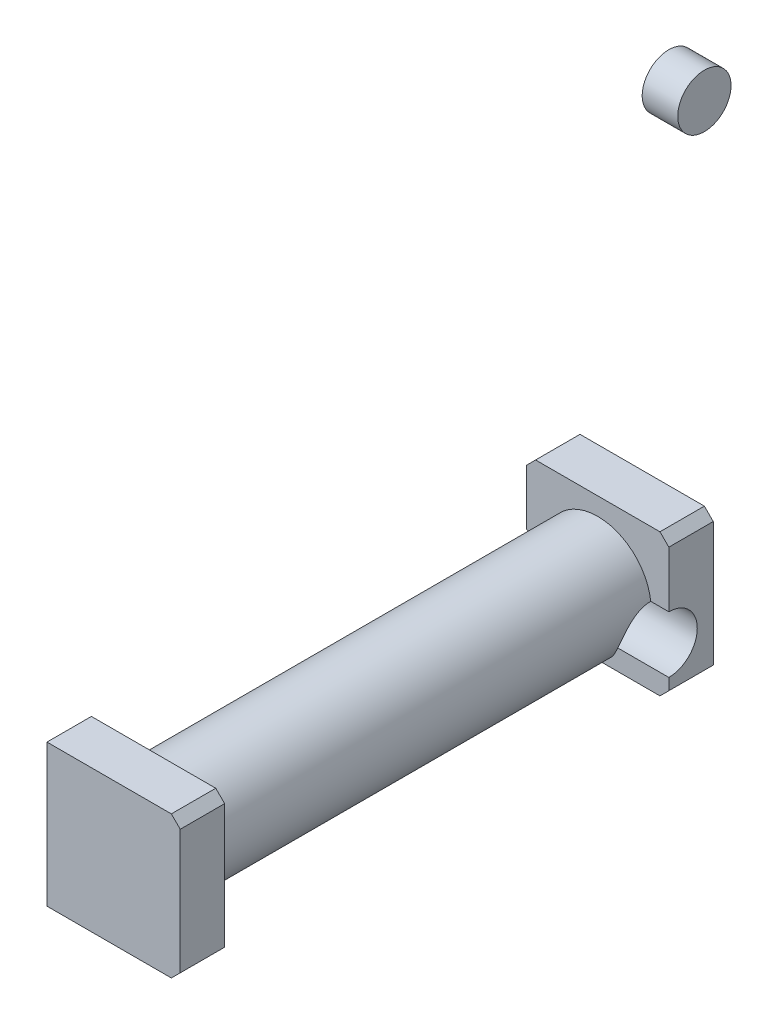
SolidWorks part; units mm, degrees
ref_plane "前视基准面" through (0, 0, 0) normal (0, 0, 1) x (1, 0, 0)
ref_plane "上视基准面" through (0, 0, 0) normal (0, 1, 0) x (1, 0, 0)
ref_plane "右视基准面" through (0, 0, 0) normal (1, 0, 0) x (0, 0, -1)
other "Configuration Table"
sketch "Sketch1" plane through (0, 0, 0) normal (0, 0, 1) x (1, 0, 0)
  circle A0 centre (0, 0) radius 30
extrude "Boss-Extrude1" add sketch "Sketch1" along normal blind 250
sketch "Sketch2" plane through (0, 0, 0) normal (0, 0, 1) x (1, 0, 0)
  line L1 (-40, -40) -> (40, -40)
  line L2 (-40, -40) -> (-40, 40)
  line L3 (-40, 40) -> (40, 40)
  line L4 (40, -40) -> (40, 40)
  line L5 (-40, -40) -> (40, 40) construction
  line L6 (-40, 40) -> (40, -40) construction
  point P0 (0, 0)
extrude "Boss-Extrude2" add sketch "Sketch2" against normal blind 25
ref_plane "BotBlock_Face_XNeg" through (-40, 0, 0) normal (1, 0, 0) x (0, 0, -1)
sketch "Sketch3" plane through (-40, 0, 0) normal (1, 0, 0) x (0, 0, -1)
  line L0 (0, 30) -> (0, -30) construction
  circle A0 centre (0, -12.5) radius 16
extrude "Cut-Extrude1" cut sketch "Sketch3" along normal blind 80
chamfer "Chamfer1" distance 5 angle 45 4 edges at (40, 40, -12.5) (40, -40, -12.5) (-40, 40, -12.5) (-40, -40, -12.5)
sketch "Sketch4" plane through (0, 0, 0) normal (0, 0, 1) x (1, 0, 0)
  line L1 (-40, -40) -> (40, -40)
  line L2 (-40, -40) -> (-40, 40)
  line L3 (-40, 40) -> (40, 40)
  line L4 (40, -40) -> (40, 40)
  line L5 (-40, -40) -> (40, 40) construction
  line L6 (-40, 40) -> (40, -40) construction
  point P0 (0, 0)
ref_plane "TopBlock_Base_Plane" through (0, 0, 250) normal (0, 0, 1) x (1, 0, 0)
sketch "Sketch5" plane through (0, 0, 250) normal (0, 0, 1) x (1, 0, 0)
  line L1 (-40, -40) -> (40, -40)
  line L2 (-40, -40) -> (-40, 40)
  line L3 (-40, 40) -> (40, 40)
  line L4 (40, -40) -> (40, 40)
  line L5 (-40, -40) -> (40, 40) construction
  line L6 (-40, 40) -> (40, -40) construction
  point P0 (0, 0)
extrude "Boss-Extrude3" add sketch "Sketch5" along normal blind 25
ref_plane "TopBlock_Face_XPos" through (40, 0, 0) normal (1, 0, 0) x (0, 0, -1)
sketch "Sketch6" plane through (40, 0, 0) normal (1, 0, 0) x (0, 0, -1)
  circle A0 centre (0, 262.5) radius 15
extrude "Boss-Extrude4" add sketch "Sketch6" along normal blind 20
chamfer "Chamfer4" distance 5 angle 45 4 edges at (40, 40, 262.5) (40, -40, 262.5) (-40, 40, 262.5) (-40, 0, 275)
ref_plane "link2_bottom_side_face_hole" through (-40, 0, 0) normal (1, 0, 0) x (0, 0, -1)
ref_plane "link2_top_side_face_pin_base" through (40, 0, 0) normal (1, 0, 0) x (0, 0, -1)
sketch3d "3DSketch1"
  line L0 (-40, 0, -12.5) -> (40, 0, -12.5) construction
ref_axis "link2_bottom_side_hole_axis" through (-40, 0, -12.5) along (1, 0, 0)
sketch3d "3DSketch2"
  line L0 (40, 0, 262.5) -> (60, 0, 262.5) construction
ref_axis "link2_top_pin_axis" through (40, 0, 262.5) along (1, 0, 0)
